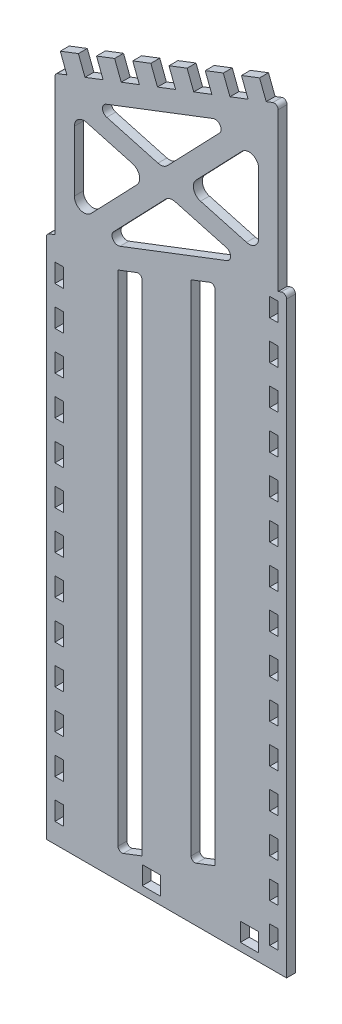
SolidWorks part; units mm, degrees
ref_plane "Front Plane" through (0, 0, 0) normal (0, 0, 1) x (1, 0, 0)
ref_plane "Top Plane" through (0, 0, 0) normal (0, 1, 0) x (1, 0, 0)
ref_plane "Right Plane" through (0, 0, 0) normal (1, 0, 0) x (0, 0, -1)
sketch "Sketch1" plane through (0, 0, 0) normal (0, 0, 1) x (1, 0, 0)
  line L0 (-36.5179, 109.22) -> (36.5179, 109.22) construction
  line L1 (-36.5179, 109.22) -> (36.5179, 137.2558)
  line L2 (-36.5179, 109.22) -> (-36.5179, -109.22)
  line L3 (-36.5179, -109.22) -> (36.5179, -109.22)
  line L4 (36.5179, 137.2558) -> (36.5179, -109.22)
  point P4 (0, 123.2379)
  point P7 (-36.5179, 0)
  dimension "D1" = 78.232
  dimension "D2" = 218.44
  dimension "D3" = 21
extrude "Boss-Extrude1" add sketch "Sketch1" along normal mid plane 2.921
sketch "Sketch2" plane through (0, 0, 1.4605) normal (0, 0, 1) x (1, 0, 0)
  line L0 (-36.5179, -109.22) -> (-33.5969, -109.22)
  line L1 (-36.5179, 109.22) -> (36.5179, 109.22)
  line L2 (-36.5179, 109.22) -> (-36.5179, -109.22)
  line L4 (36.5179, 109.22) -> (36.5179, -109.22)
  line L5 (-36.5179, 109.22) -> (-33.5969, 109.22)
  line L6 (-36.5179, 109.22) -> (-36.5179, -109.22)
  line L7 (-36.5179, -109.22) -> (-33.5969, -109.22)
  line L8 (-33.5969, 109.22) -> (-33.5969, -109.22)
  line L9 (36.5179, -109.22) -> (33.5969, -109.22)
  line L10 (36.5179, -109.22) -> (36.5179, 109.22)
  line L11 (36.5179, 109.22) -> (33.5969, 109.22)
  line L12 (33.5969, -109.22) -> (33.5969, 109.22)
  line L13 (33.5969, -109.22) -> (36.5179, -109.22)
  line L14 (-33.5969, -109.22) -> (33.5969, -109.22)
  line L29 (0, 123.2379) -> (0, -109.22) construction
  line L31 (36.5179, 137.2558) -> (-36.5179, 109.22) construction
  point P16 (0, -109.22)
  dimension "D1" = 2.921
  dimension "D2" = 2.921
sketch "Sketch3" plane through (-41.2311, 107.4108, 0) normal (-0.3584, 0.9336, 0) x (0.9336, 0.3584, 0)
  line L0 (83.2805, 1.4605) -> (5.0485, 1.4605) construction
  line L1 (79.0895, 1.4605) -> (72.7395, 1.4605)
  line L2 (79.0895, 1.4605) -> (79.0895, -1.4605)
  line L3 (79.0895, -1.4605) -> (72.7395, -1.4605)
  line L4 (72.7395, 1.4605) -> (72.7395, -1.4605)
  line L5 (83.2805, -1.4605) -> (5.0485, -1.4605) construction
  line L6 (83.2805, -1.4605) -> (83.2805, 1.4605) construction
  line L7 (66.3895, 1.4605) -> (66.3895, -1.4605)
  line L8 (66.3895, 1.4605) -> (60.0395, 1.4605)
  line L9 (60.0395, 1.4605) -> (60.0395, -1.4605)
  line L10 (66.3895, -1.4605) -> (60.0395, -1.4605)
  line L11 (53.6895, 1.4605) -> (53.6895, -1.4605)
  line L12 (53.6895, 1.4605) -> (47.3395, 1.4605)
  line L13 (47.3395, 1.4605) -> (47.3395, -1.4605)
  line L14 (53.6895, -1.4605) -> (47.3395, -1.4605)
  line L15 (40.9895, 1.4605) -> (40.9895, -1.4605)
  line L16 (40.9895, 1.4605) -> (34.6395, 1.4605)
  line L17 (34.6395, 1.4605) -> (34.6395, -1.4605)
  line L18 (40.9895, -1.4605) -> (34.6395, -1.4605)
  line L19 (28.2895, 1.4605) -> (28.2895, -1.4605)
  line L20 (28.2895, 1.4605) -> (21.9395, 1.4605)
  line L21 (21.9395, 1.4605) -> (21.9395, -1.4605)
  line L22 (28.2895, -1.4605) -> (21.9395, -1.4605)
  line L23 (15.5895, 1.4605) -> (15.5895, -1.4605)
  line L24 (15.5895, 1.4605) -> (9.2395, 1.4605)
  line L25 (9.2395, 1.4605) -> (9.2395, -1.4605)
  line L26 (15.5895, -1.4605) -> (9.2395, -1.4605)
  line L27 (79.0895, 1.4605) -> (66.3895, 1.4605) construction
  point P10 (72.7395, 0)
  dimension "D1" = 4.191
  dimension "D2" = 6.35
  dimension "D4" = 12.7
  dimension "D3" = 6
extrude "Boss-Extrude2" add sketch "Sketch3" along normal blind 6.0452
sketch "Sketch5" plane through (0, 0, 1.4605) normal (0, 0, 1) x (1, 0, 0)
  line L0 (0, 123.2379) -> (0, -109.22) construction
  line L1 (-15.875, 63.8041) -> (-8.001, 66.8266)
  line L2 (-15.875, 63.8041) -> (-15.875, -101.2959)
  line L3 (-15.875, -101.2959) -> (-8.001, -98.2734)
  line L4 (-8.001, 66.8266) -> (-8.001, -98.2734)
  line L5 (8.001, 72.9692) -> (15.875, 75.9918)
  line L6 (8.001, 72.9692) -> (8.001, -92.1308)
  line L7 (8.001, -92.1308) -> (15.875, -89.1082)
  line L8 (15.875, 75.9918) -> (15.875, -89.1082)
  line L9 (-36.5179, -109.22) -> (36.5179, -109.22) construction
  line L11 (-33.5969, -109.22) -> (33.5969, -109.22) construction
  line L12 (-8.001, 66.8266) -> (8.001, 72.9692) construction
  line L13 (-20.7488, 115.2732) -> (-26.6771, 112.9976) construction
  line L14 (-36.5179, -109.22) -> (36.5179, -81.1842) construction
  line L15 (36.5179, -109.22) -> (36.5179, 137.2558) construction
  line L17 (36.5179, -109.22) -> (36.5179, 137.2558) construction
  line L20 (-36.5179, 109.22) -> (-36.5179, -109.22) construction
  line L22 (-32.6053, 110.7219) -> (-36.5179, 109.22) construction
  line L23 (2.9641, 124.3757) -> (-2.9641, 122.1001) construction
  point P16 (0, 69.8979)
  dimension "D1" = 31.75
  dimension "D2" = 21
  dimension "D3" = 165.1
  dimension "D4" = 7.874
extrude "Cut-Extrude2" cut sketch "Sketch5" against normal through all
sketch "Sketch6" plane through (0, 0, 1.4605) normal (0, 0, 1) x (1, 0, 0)
  line L0 (-39.2679, 54.8244) -> (39.2679, 84.9715)
  line L1 (39.2679, 84.9715) -> (39.2679, -109.22)
  line L2 (39.2679, -109.22) -> (-39.2679, -109.22)
  line L3 (-39.2679, -109.22) -> (-39.2679, 54.8244)
  line L4 (-8.001, 66.8266) -> (-15.875, 63.8041) construction
  line L5 (-36.5179, 109.22) -> (-36.5179, -109.22) construction
  line L6 (36.5179, -109.22) -> (36.5179, 137.2558) construction
  line L7 (-36.5179, -109.22) -> (36.5179, -109.22) construction
  line L8 (-36.5179, 55.88) -> (-36.5179, -109.22)
  line L9 (36.5179, -109.22) -> (36.5179, 83.9158)
  line L10 (0, -109.22) -> (0, 69.8979) construction
  line L11 (-36.5179, -96.647) -> (-33.7679, -96.647)
  line L12 (-36.5179, -96.647) -> (-36.5179, -102.743)
  line L13 (-36.5179, -102.743) -> (-33.7679, -102.743)
  line L14 (-33.7679, -96.647) -> (-33.7679, -102.743)
  line L15 (36.5179, -102.743) -> (33.7679, -102.743)
  line L16 (33.7679, -96.647) -> (33.7679, -102.743)
  line L17 (36.5179, -96.647) -> (33.7679, -96.647)
  line L18 (36.5179, -96.647) -> (36.5179, -102.743)
  line L19 (-39.2679, 54.8244) -> (-39.2679, 62.4444)
  line L20 (-39.2679, 62.4444) -> (-36.5179, 63.5)
  line L21 (-36.5179, 63.5) -> (-36.5179, 55.88)
  point P22 (-35.1429, -102.743)
  line M13 (-36.5179, 109.22) -> (-36.5179, -109.22)
  line M15 (36.5179, -109.22) -> (36.5179, 137.2558)
  dimension "D1" = 2.75
  dimension "D2" = 2.75
  dimension "D3" = 2.75
  dimension "D4" = 6.096
  dimension "D5" = 6.477
  dimension "D6" = 7.62
extrude "Boss-Extrude3" add sketch "Sketch6" against normal blind 2.921 contours L3 L2 L0 M13 | L2 L1 L0 M15 | L20 L19 L0 M13 region at (-37.8929, 59.1622, 1.4605) region at (-37.8915, -26.9336, 1.4605) region at (37.8942, -12.3879, 1.4605)
extrude "Cut-Extrude3" cut sketch "Sketch6<3>" against normal through all contours L14 L11 L8 L13 region at (-35.1429, -99.695, 1.4605)
sketch "Sketch6<3>" plane through (0, 0, 1.4605) normal (0, 0, 1) x (1, 0, 0) same geometry as "Sketch6"
extrude "Cut-Extrude4" cut sketch "Sketch6<4>" against normal through all contours L9 L17 L16 L15 region at (35.1429, -99.695, 1.4605)
sketch "Sketch6<4>" plane through (0, 0, 1.4605) normal (0, 0, 1) x (1, 0, 0) same geometry as "Sketch6"
pattern_linear "LPattern1" count 13 spacing 12.7 along (0, 1, 0) of "Cut-Extrude3"
pattern_linear "LPattern2" count 15 spacing 12.7 along (0, 1, 0) of "Cut-Extrude4"
sketch "Sketch8" plane through (0, 0, 1.4605) normal (0, 0, 1) x (1, 0, 0)
  line L0 (-36.5179, 109.22) -> (36.5179, 137.2558) construction
  line L1 (36.5179, 137.2558) -> (36.5179, 83.9158) construction
  line L2 (36.5179, 83.9158) -> (-36.5179, 55.88) construction
  line L3 (-36.5179, 55.88) -> (-36.5179, 109.22) construction
  line L4 (-30.1679, 104.8558) -> (30.1679, 88.2801) construction
  line L5 (30.1679, 128.0165) -> (-30.1679, 65.1193) construction
  line L6 (-30.1679, 65.1193) -> (-30.1679, 104.8558)
  line L7 (-30.1679, 104.8558) -> (30.1679, 128.0165)
  line L8 (30.1679, 128.0165) -> (30.1679, 88.2801)
  line L9 (30.1679, 88.2801) -> (-30.1679, 65.1193)
  line L10 (27.8767, 130.2145) -> (-32.4592, 67.3172)
  line L11 (-31.009, 101.7942) -> (29.3268, 85.2185)
  line L12 (32.4592, 125.8186) -> (-27.8767, 62.9214)
  line L13 (-29.3268, 107.9173) -> (31.009, 91.3416)
  dimension "D1" = 6.35
  dimension "D2" = 3.175
  dimension "D3" = 3.175
extrude "Cut-Extrude5" cut sketch "Sketch8" against normal through all contours L11 L6 L10 | L11 L12 L9 | L7 L13 L10 | L12 L13 L8 region at (-22.1059, 88.7292, 1.4605) region at (0.9822, 82.3863, 1.4605) region at (-0.9822, 110.7495, 1.4605) region at (22.1059, 104.4067, 1.4605)
fillet "Fillet1" radius 1.27 8 edges at (8.001, -92.1308, 0) (-15.875, -101.2959, 0) (-8.001, 66.8266, 0) (15.875, 75.9918, 0) (-39.2679, 62.4444, 0) (39.2679, 84.9715, 0) (-36.5179, 109.22, 0) (36.5179, 137.2558, 0)
fillet "Fillet2" radius 3.175 8 edges at (30.1679, 91.5727, 0) (30.1679, 123.4301, 0) (-30.1679, 69.7057, 0) (-30.1679, 101.5631, 0) (-5.9818, 94.9186, 0) (5.9818, 98.2172, 0) (0.9822, 93.0054, 0) (-0.9822, 100.1304, 0)
fillet "Fillet3" radius 1.905 4 edges at (-23.2039, 67.7925, 0) (25.1684, 86.3609, 0) (23.2039, 125.3433, 0) (-25.1684, 106.7749, 0)
sketch "Sketch9" plane through (0, 0, 1.4605) normal (0, 0, 1) x (1, 0, 0)
  line L1 (-7.9321, -100.68) -> (-1.9321, -100.68)
  line L2 (-7.9321, -100.68) -> (-7.9321, -106.68)
  line L3 (-7.9321, -106.68) -> (-1.9321, -106.68)
  line L4 (-1.9321, -100.68) -> (-1.9321, -106.68)
  line L5 (24.1679, -100.68) -> (30.1679, -100.68)
  line L6 (24.1679, -100.68) -> (24.1679, -106.68)
  line L7 (24.1679, -106.68) -> (30.1679, -106.68)
  line L8 (30.1679, -100.68) -> (30.1679, -106.68)
  line L9 (36.5179, -102.743) -> (36.5179, -96.647) construction
  line L10 (-39.2679, -109.22) -> (39.2679, -109.22) construction
  dimension "D1" = 38.1
  dimension "D2" = 6.35
  dimension "D3" = 6
  dimension "D4" = 6
  dimension "D5" = 6
  dimension "D6" = 2.54
extrude "Cut-Extrude6" cut sketch "Sketch9" against normal through all
